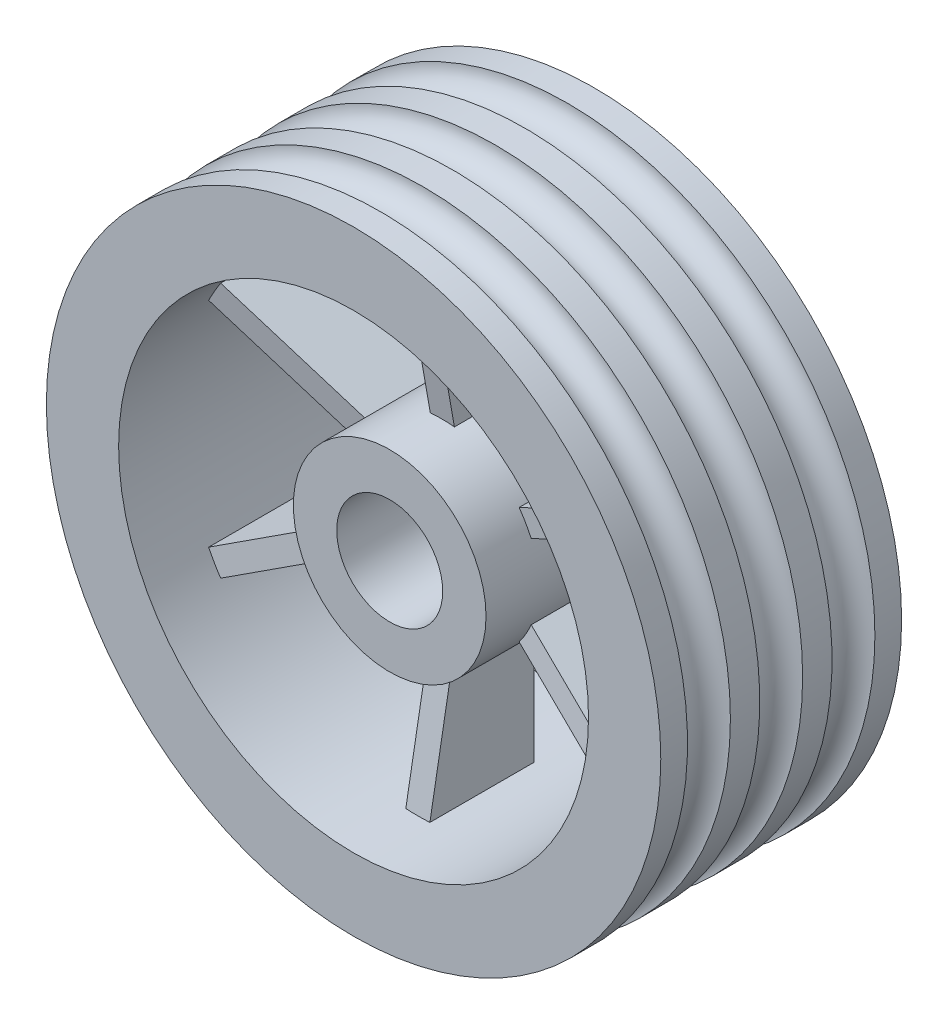
SolidWorks part; units mm, degrees
ref_plane "Front Plane" through (0, 0, 0) normal (0, 0, 1) x (1, 0, 0)
ref_plane "Top Plane" through (0, 0, 0) normal (0, 1, 0) x (1, 0, 0)
ref_plane "Right Plane" through (0, 0, 0) normal (1, 0, 0) x (0, 0, -1)
sketch "Sketch1" plane through (0, 0, 0) normal (0, 0, 1) x (1, 0, 0)
  circle A0 centre (0, 0) radius 9.755
  circle A1 centre (0, 0) radius 12.755
  dimension "D2" = 25.51
  dimension "D1" = 3
extrude "Boss-Extrude1" add sketch "Sketch1" along normal blind 10
sketch "Sketch2" plane through (0, 0, 0) normal (0, 0, 1) x (1, 0, 0)
  circle A0 centre (0, 0) radius 4
  circle A1 centre (0, 0) radius 2.2
  dimension "D1" = 8
  dimension "D2" = 4.4
extrude "Boss-Extrude2" add sketch "Sketch2" along normal blind 8.5 separate body
sketch "Sketch5" plane through (0, 0, 0) normal (1, 0, 0) x (0, 0, -1)
  line L6 (-3, 2.2) -> (-3, 10.7)
  line L7 (-3, 10.7) -> (-7.5, 10.7)
  line L8 (-7.5, 10.7) -> (-6, 2.2)
  line L9 (-6, 2.2) -> (-3, 2.2)
  point P3 (0, 0)
  dimension "D1" = 2.2
  dimension "D2" = 3
  dimension "D3" = 3
  dimension "D4" = 4.5
  dimension "D5" = 8.5
extrude "Boss-Extrude3" add sketch "Sketch5" along normal blind 0.5 and the other way blind 0.5
sketch "Sketch6" plane through (0, 0, 0) normal (1, 0, 0) x (0, 0, -1)
  line L0 (0, 0) -> (-8.5, 0) construction
  line L1 (-8.5, 2.2) -> (-8.5, -2.2) construction
  line L2 (-8.5, 0) -> (-8.5, 5) construction
  line L3 (-8.5, 5) -> (-10, 9.755)
  line L4 (-10, 12.755) -> (-10, -12.755) construction
  line L5 (-10, 9.755) -> (-10, -9.755) construction
  line L7 (-7, 5) -> (-7, 9.755)
  line L8 (-7, 9.755) -> (-10, 9.755)
  line L9 (-8.5, 5) -> (-8.5, 3.4839)
  line L10 (-8.5, 3.4839) -> (-7, 3.4839)
  line L11 (-7, 3.4839) -> (-7, 5)
  dimension "D1" = 5
  dimension "D2" = 1.5
  dimension "D3" = 4.755
extrude "Boss-Extrude8" [suppressed] add sketch "Sketch6" along normal blind 0.5 and the other way blind 0.5
pattern_circular "CirPattern1" count 6 over 360 about axis through (0, 0, 8.5) along (0, 0, -1) of "Boss-Extrude3", "Boss-Extrude8" reverse direction yes
sketch "Sketch7" plane through (0, 0, 0) normal (1, 0, 0) x (0, 0, -1)
  line L0 (0, 0) -> (0, 12.755) construction
  line L1 (0, -2.2) -> (0, 2.2) construction
  line L2 (0, -12.755) -> (0, 12.755) construction
  line L3 (0, 12.755) -> (-10, 12.755) construction
  line L4 (-10, 12.755) -> (-10, -12.755) construction
  line L5 (0, 0) -> (-10.5402, 0) construction
  circle A0 centre (-5, 12.755) radius 0.89
  circle A1 centre (-2, 12.755) radius 0.89
  circle A2 centre (-8, 12.755) radius 0.89
  dimension "D3" = 1.78
  dimension "D1" = 12.755
  dimension "D2" = 10
  dimension "D6" = 3
  dimension "D7" = 3
  dimension "D4" = 2
  dimension "D5" = 2
revolve "Cut-Revolve1" cut sketch "Sketch7" angle 360 about L5
ref_plane "Plane1" through (0, 0, 2) normal (0, 0, -1) x (-1, 0, 0)
ref_plane "Plane2" through (0, 0, 5) normal (0, 0, -1) x (-1, 0, 0)
ref_plane "Plane3" through (0, 0, 8) normal (0, 0, -1) x (-1, 0, 0)
